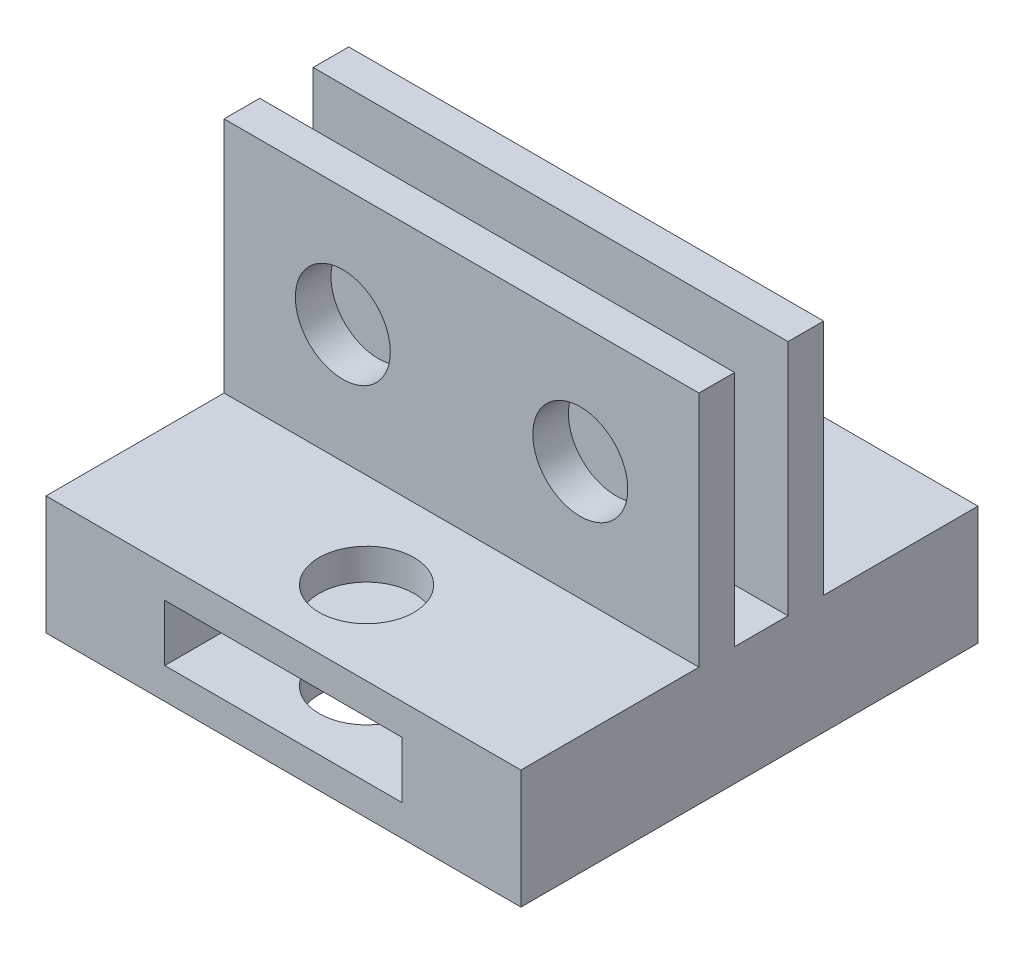
SolidWorks part; units mm, degrees
ref_plane "Front Plane" through (0, 0, 0) normal (0, 0, 1) x (1, 0, 0)
ref_plane "Top Plane" through (0, 0, 0) normal (0, 1, 0) x (1, 0, 0)
ref_plane "Right Plane" through (0, 0, 0) normal (1, 0, 0) x (0, 0, -1)
sketch "Sketch1" plane through (0, 0, 0) normal (0, 0, 1) x (1, 0, 0)
  line L1 (-296.042, -120) -> (-0.042, -120) construction
  line L2 (-6.342, -100) -> (-46.342, -100)
  line L3 (-6.342, -100) -> (-6.342, -120)
  line L4 (-6.342, -120) -> (-46.342, -120)
  line L5 (-46.342, -100) -> (-46.342, -120)
  line L7 (-6.342, -120) -> (-46.342, -120)
  line L8 (-6.342, -120) -> (-6.342, -130)
  line L9 (-6.342, -130) -> (-46.342, -130)
  line L10 (-46.342, -120) -> (-46.342, -130)
  line L11 (-36.342, -122.62) -> (-16.342, -122.62)
  line L12 (-36.342, -122.62) -> (-36.342, -127.38)
  line L13 (-36.342, -127.38) -> (-16.342, -127.38)
  line L14 (-16.342, -122.62) -> (-16.342, -127.38)
  circle A0 centre (-16.342, -110) radius 4
  circle A1 centre (-36.342, -110) radius 4
  point P22 (-16.342, -125)
  dimension "D7" = 8
  dimension "D8" = 8
  dimension "D1" = 10
  dimension "D2" = 10
  dimension "D3" = 10
  dimension "D4" = 10
  dimension "D5" = 4.76
  dimension "D6" = 5
  dimension "D9" = 20
  dimension "D10" = 10
extrude "Boss-Extrude1" add sketch "Sketch1" along normal blind 3 contours L2 L5 L4 L3 A1 A0 | L4 L10 L9 L8 L11 L14 L13 L12 region at (-26.342, -110, 0) region at (-6.7543, -125, 0)
extrude "Boss-Extrude3" add sketch "Sketch1<5>" against normal blind 7.5 contours L2 L5 L4 L3 A1 A0 | L4 L10 L9 L8 L11 L14 L13 L12 region at (-26.342, -110, 0) region at (-6.7543, -125, 0)
sketch "Sketch1<5>" plane through (0, 0, 0) normal (0, 0, 1) x (1, 0, 0) same geometry as "Sketch1"
extrude "Cut-Extrude1" cut sketch "Sketch1<6>" against normal blind 4.5 contours L2 L5 L4 L3 A1 A0 region at (-26.342, -110, 0)
sketch "Sketch1<6>" plane through (0, 0, 0) normal (0, 0, 1) x (1, 0, 0) same geometry as "Sketch1"
extrude "Boss-Extrude4" add sketch "Sketch1<7>" along normal blind 18 and the other way blind 20.5 contours L4 L10 L9 L8 L11 L14 L13 L12 region at (-6.7543, -125, 0)
sketch "Sketch1<7>" plane through (0, 0, 0) normal (0, 0, 1) x (1, 0, 0) same geometry as "Sketch1"
sketch "Sketch5" plane through (0, -130, 0) normal (0, -1, 0) x (1, 0, 0)
  line L0 (-6.342, 18) -> (-46.342, 18) construction
  line L1 (-26.342, 18) -> (-26.342, 11)
  line L2 (-26.342, -13.5) -> (-26.342, -20.5)
  line L3 (-6.342, -20.5) -> (-46.342, -20.5) construction
  circle A0 centre (-26.342, 11) radius 4
  circle A1 centre (-26.342, -13.5) radius 4
  dimension "D1" = 8
  dimension "D2" = 8
  dimension "D3" = 7
  dimension "D4" = 7
extrude "Cut-Extrude2" cut sketch "Sketch5" against normal blind 10 contours A0 | A1 region at (-29.0904, -130, 8.2516) region at (-23.5936, -130, -16.2484)
